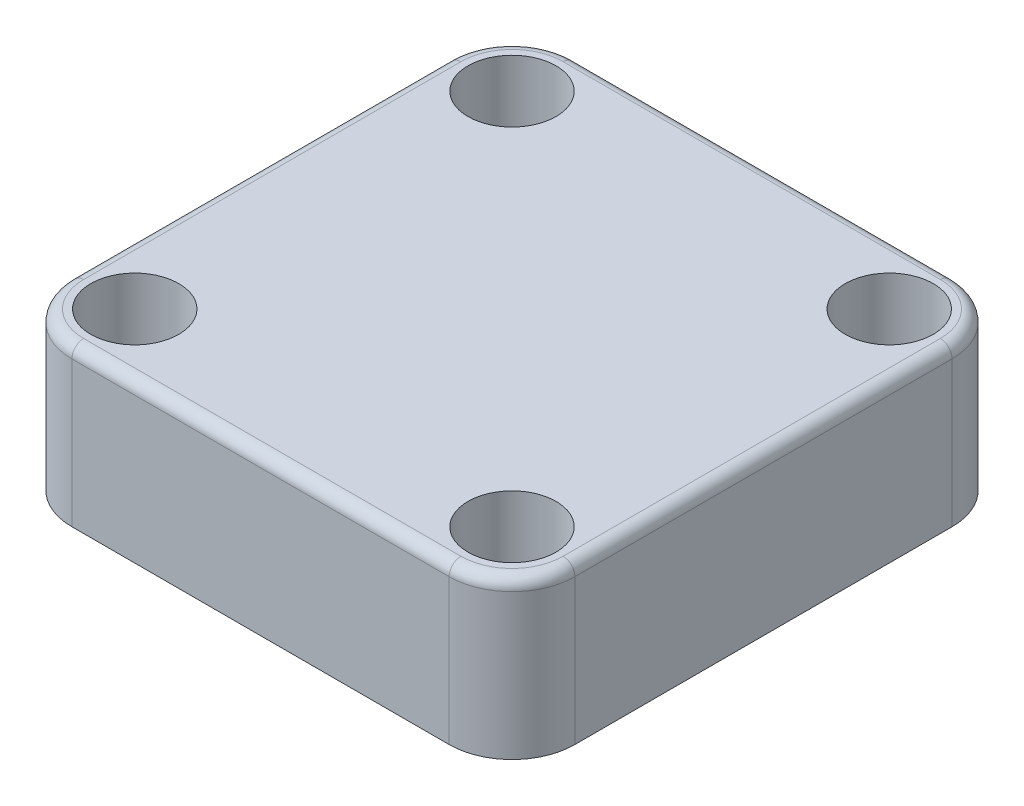
SolidWorks part; units mm, degrees
ref_plane "Front Plane" through (0, 0, 0) normal (0, 0, 1) x (1, 0, 0)
ref_plane "Top Plane" through (0, 0, 0) normal (0, 1, 0) x (1, 0, 0)
ref_plane "Right Plane" through (0, 0, 0) normal (1, 0, 0) x (0, 0, -1)
sketch "Sketch1" plane through (0, 0, 0) normal (0, 1, 0) x (1, 0, 0)
  line L0 (-16, 12) -> (-16, -12)
  line L1 (-12, 12) -> (12, 12)
  line L2 (-12, 12) -> (-12, -12)
  line L3 (-12, -12) -> (12, -12)
  line L4 (12, 12) -> (12, -12)
  line L5 (-12, 12) -> (12, -12) construction
  line L6 (-12, -12) -> (12, 12) construction
  line L7 (-12, -16) -> (12, -16)
  line L8 (16, 12) -> (16, -12)
  line L9 (-12, 16) -> (12, 16)
  circle A0 centre (-12, 12) radius 1.6
  circle A1 centre (12, 12) radius 1.6
  circle A2 centre (12, -12) radius 1.6
  circle A3 centre (-12, -12) radius 1.6
  circle A4 centre (-12, 12) radius 4
  circle A5 centre (12, 12) radius 4
  circle A6 centre (12, -12) radius 4
  circle A7 centre (-12, -12) radius 4
  point P0 (0, 0)
  point P22 (12, 16)
  dimension "D2" = 3.2
  dimension "D3" = 8
  dimension "D1" = 24
extrude "Boss-Extrude1" add sketch "Sketch1" along normal blind 10 contours A5 L9 A4 L1 | L1 A4 L2 A0 | A7 L2 A4 L0 | A7 L3 A3 L2 | A7 L7 A6 L3 | A6 L4 A2 L3 | A6 L8 A5 L4 | A7 L3 A6 L4 A5 L1 A4 L2 | L4 A6 L3 A2 | L3 A7 L2 A3 | L2 A4 L1 A0 | L4 A5 L1 A1 | L1 A5 L4 A1 region at (-14.1072, 0, 0) region at (-14.7484, 0, -14.7484) region at (-14.7484, 0, 9.2516) region at (0, 0, -14.1072) region at (0, 0, 0) region at (-10.1083, 0, -10.1083) region at (0, 0, 14.1072) region at (-10.1083, 0, 10.1083) region at (14.7484, 0, -14.7484) region at (9.2516, 0, 14.7484) region at (14.1072, 0, 0) region at (10.1083, 0, -10.1083) region at (10.1083, 0, 10.1083)
sketch "Sketch2" plane through (0, 0, 0) normal (0, -1, 0) x (1, 0, 0)
  line L0 (-12, 16) -> (12, 16) construction
  line L1 (9, -16) -> (-9, -16)
  line L2 (9, -16) -> (9, 16)
  line L3 (9, 16) -> (-9, 16)
  line L4 (-9, -16) -> (-9, 16)
  line L5 (9, -16) -> (-9, 16) construction
  line L6 (9, 16) -> (-9, -16) construction
  circle A0 centre (0, 0) radius 14
  circle A3 centre (-12, 12) radius 1.6 construction
  circle A4 centre (-12, 12) radius 1.6
  point P10 (0, 0)
  line M12 (-12, -16) -> (12, -16)
  dimension "D1" = 28
  dimension "D2" = 3
extrude "Cut-Extrude1" cut sketch "Sketch2" against normal offset from surface (8.5 mm away) 1.5 contours A0 L4 L2 M12 | A0 region at (0, 0, -14.3317) up to face at (-12, 10, 13.6)
sketch "Sketch3" plane through (0, 10, 0) normal (0, 1, 0) x (1, 0, 0)
  circle A0 centre (-12, 12) radius 2.8
  circle A1 centre (12, 12) radius 2.8
  circle A2 centre (12, -12) radius 2.8
  circle A3 centre (-12, -12) radius 2.8
  dimension "D1" = 5.6
extrude "Cut-Extrude2" cut sketch "Sketch3" against normal offset from surface (8 mm away) 2 up to face at (0, 0, -2.3937)
fillet "Fillet1" radius 6 2 edges at (-9, 4.25, -10.7238) (9, 4.25, -10.7238)
fillet "Fillet2" radius 3 5 edges at (9, 8.5, -14.6144) (9.3875, 8.5, -11.1074) (-9, 8.5, -14.6144) (-9.3875, 8.5, -11.1074) (0, 8.5, 14)
fillet "Fillet3" radius 0.75 8 edges at (-14.8284, 10, 14.8284) (-16, 10, 0) (-14.8284, 10, -14.8284) (0, 10, -16) (14.8284, 10, -14.8284) (16, 10, 0) (14.8284, 10, 14.8284) (0, 10, 16)
